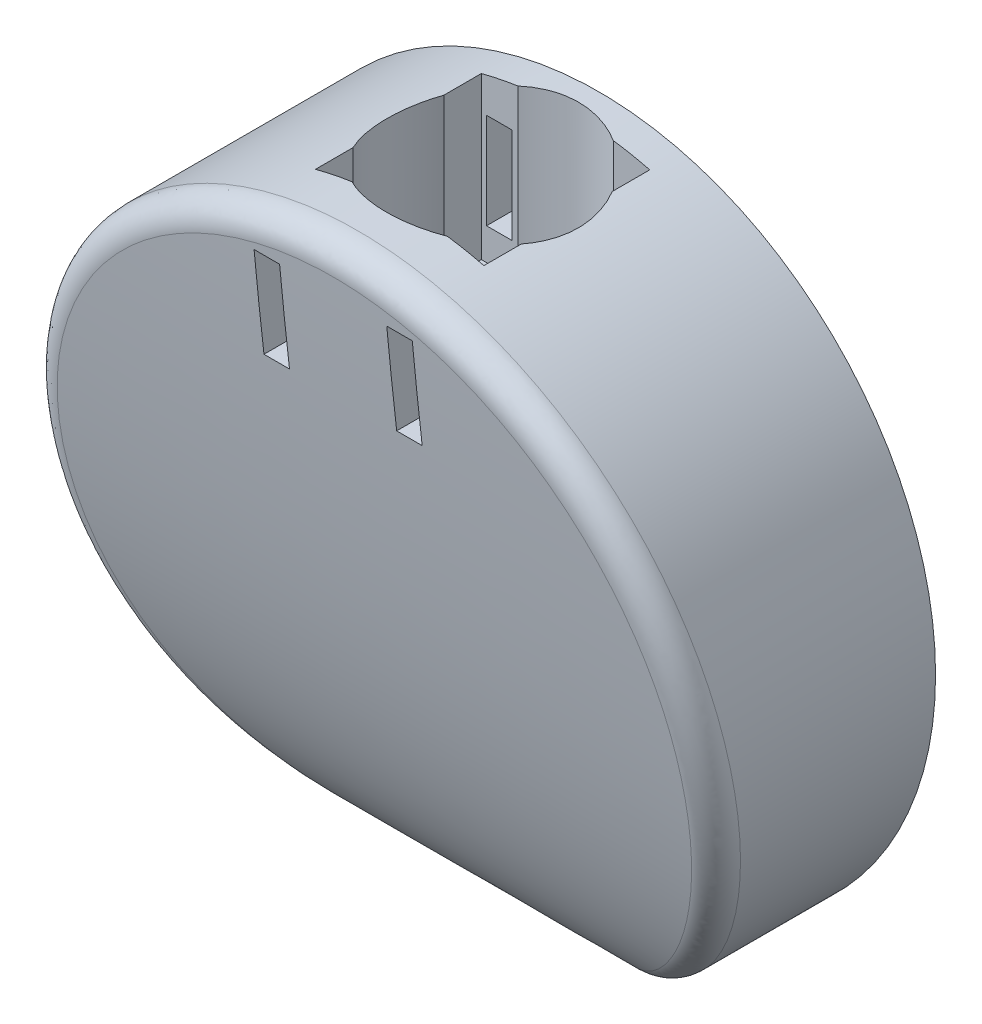
SolidWorks part; units mm, degrees
ref_plane "Plan de face" through (0, 0, 0) normal (0, 0, 1) x (1, 0, 0)
ref_plane "Plan de dessus" through (0, 0, 0) normal (0, 1, 0) x (1, 0, 0)
ref_plane "Plan de droite" through (0, 0, 0) normal (1, 0, 0) x (0, 0, -1)
sketch "Esquisse1" plane through (0, 0, 0) normal (0, 0, 1) x (1, 0, 0)
  circle A0 centre (0.2907, 0.2907) radius 67
  dimension "D1" = 134
extrude "Boss.-Extru.1" add sketch "Esquisse1" along normal blind 53.34
sketch "Esquisse4" plane through (0, 0, 0) normal (1, 0, 0) x (0, 0, -1)
  line L1 (-0.1422, -67.1272) -> (-53.34, -66.7093)
  line L2 (-53.34, -66.7093) -> (-53.34, 67.2907)
  spline S0 degree 3 poles (-53.34, 67.2907) (-53.3149, 64.9653) (-44.6519, -34.8903) (-23.1604, -66.3734) (-0.1422, -67.1272) knots 0 0 0 0 0.36297 1 1 1 1
extrude "Enlèv. mat.-Extru.1" cut sketch "Esquisse4" against normal through all both and the other way through all
fillet "Congé1" radius 5 1 edges at (-0.0427, -66.7085, 4.6747)
ref_plane "Plan2" through (0, 67.2907, 0) normal (0, 1, 0) x (1, 0, 0)
sketch "Esquisse6" plane through (0, 67.2907, 0) normal (0, 1, 0) x (1, 0, 0)
  line L0 (67.2907, 0) -> (-66.7093, 0) construction
  line L1 (-16.7833, -6.35) -> (-9.5231, -6.35)
  line L2 (-16.7833, -6.35) -> (-16.7833, -13.8118)
  line L3 (-16.7833, -39.37) -> (-9.5231, -39.37)
  line L4 (16.7447, -6.35) -> (16.7447, -13.8118)
  line L5 (67.2907, -40.0395) -> (67.2907, 0) construction
  line L6 (-16.7833, -31.9082) -> (-16.7833, -39.37)
  line L7 (9.4845, -39.37) -> (16.7447, -39.37)
  line L8 (16.7447, -31.9082) -> (16.7447, -39.37)
  line L9 (9.4845, -6.35) -> (16.7447, -6.35)
  arc A0 (-16.7833, -13.8118) -> (-16.7833, -31.9082) centre (-0.0193, -22.86) ccw
  arc A1 (-9.5231, -39.37) -> (9.4845, -39.37) centre (-0.0193, -22.86) ccw
  arc A2 (16.7447, -31.9082) -> (16.7447, -13.8118) centre (-0.0193, -22.86) ccw
  arc A3 (9.4845, -6.35) -> (-9.5231, -6.35) centre (-0.0193, -22.86) ccw
  dimension "D5" = 38.1
  dimension "D1" = 33.528
  dimension "D2" = 33.02
  dimension "D3" = 22.86
  dimension "D4" = 67.31
  dimension "D6" = 16.51
  dimension "D7" = 16.764
extrude "Enlèv. mat.-Extru.4" cut sketch "Esquisse6" against normal blind 34.29
sketch "Esquisse7" plane through (0, 67.2907, 0) normal (0, 1, 0) x (1, 0, 0)
  circle A0 centre (-0.0193, -22.86) radius 3.302
  arc A1 (9.4845, -6.35) -> (-9.5231, -6.35) centre (-0.0193, -22.86) ccw construction
  dimension "D1" = 6.604
extrude "Enlèv. mat.-Extru.5" cut sketch "Esquisse7" against normal blind 63.5
ref_plane "Plan4" through (0, 0, 6.35) normal (0, 0, 1) x (1, 0, 0)
sketch "Esquisse10" plane through (0, 0, 6.35) normal (0, 0, 1) x (1, 0, 0)
  line L1 (-15.7461, 58.4007) -> (-10.6661, 58.4007)
  line L2 (-15.7461, 58.4007) -> (-15.7461, 39.3507)
  line L3 (-15.7461, 39.3507) -> (-10.6661, 39.3507)
  line L4 (-10.6661, 58.4007) -> (-10.6661, 39.3507)
  line L5 (-9.5231, 33.0007) -> (-9.5231, 66.5681) construction
  line L7 (-9.5231, 33.0007) -> (-16.7833, 33.0007) construction
  dimension "D1" = 5.08
  dimension "D2" = 19.05
  dimension "D3" = 1.143
  dimension "D4" = 6.35
extrude "Enlèv. mat.-Extru.7" cut sketch "Esquisse10" against normal through all
mirror "Symétrie1" about plane through (0, 0, 0) normal (1, 0, 0) of "Enlèv. mat.-Extru.7"
ref_plane "Plan5" through (0, 0, 22.8591) normal (0, 0, -1) x (-1, 0, 0)
mirror "Symétrie2" about plane through (0, 0, 22.8591) normal (0, 0, -1) of "Symétrie1", "Enlèv. mat.-Extru.7"
sketch "Esquisse12" [suppressed] plane through (15.7461, 0, 0) normal (-1, 0, 0) x (0, 0, 1)
  line L0 (52.6258, 58.4007) -> (50.6529, 39.3507)
  line L1 (50.6529, 39.3507) -> (39.37, 39.3507)
  line L2 (39.37, 39.3507) -> (39.37, 58.4007)
  line L3 (39.37, 58.4007) -> (52.6258, 58.4007)
  line L4 (52.6258, 58.4007) -> (39.37, 58.4007) construction
  line L5 (50.6529, 39.3507) -> (39.37, 39.3507) construction
  point P6 (0, 0)
  point P7 (0, 0)
  point P8 (0, 0)
  point P10 (39.4258, 39.3897)
  point P14 (0, 0)
  point P16 (0, 0)
  point P18 (0, 0)
